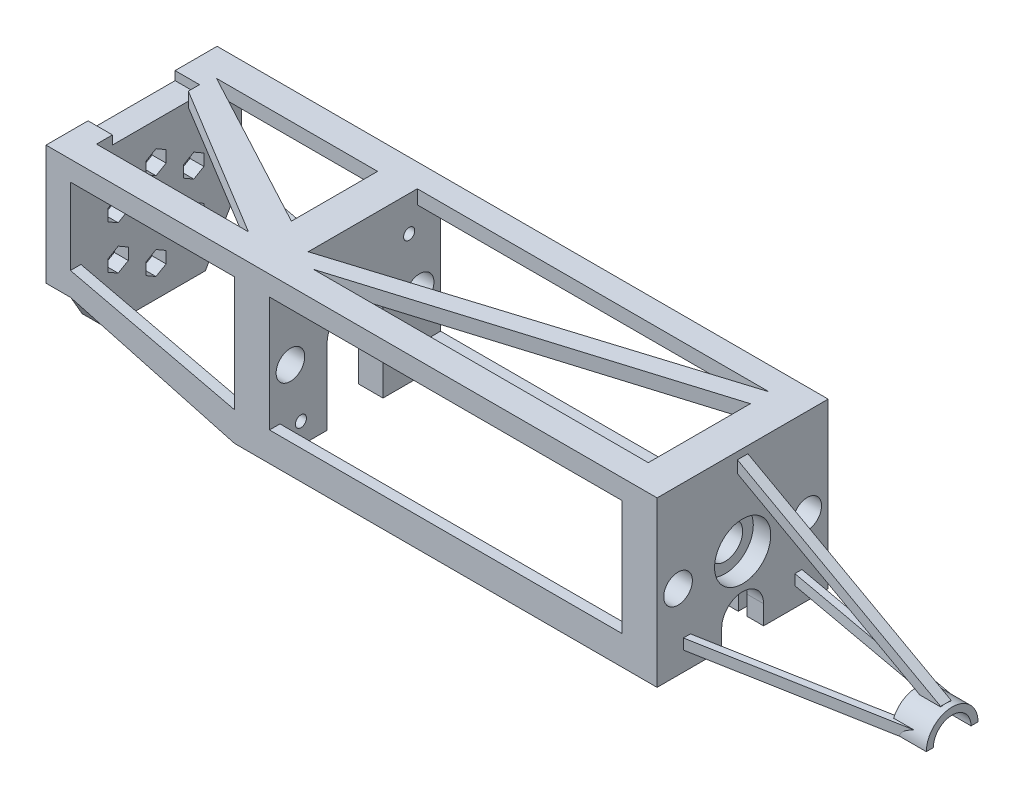
SolidWorks part; units mm, degrees
ref_plane "Front Plane" through (0, 0, 0) normal (0, 0, 1) x (1, 0, 0)
ref_plane "Top Plane" through (0, 0, 0) normal (0, 1, 0) x (1, 0, 0)
ref_plane "Right Plane" through (0, 0, 0) normal (1, 0, 0) x (0, 0, -1)
sketch "Sketch1" plane through (0, 0, 0) normal (0, 1, 0) x (1, 0, 0)
  line L0 (-33.5, 41.2067) -> (2.5, 41.2067) construction
  line L1 (-87.5, -21.5) -> (87.5, -21.5)
  line L2 (-87.5, -21.5) -> (-87.5, 21.5)
  line L3 (-87.5, 21.5) -> (87.5, 21.5)
  line L4 (87.5, -21.5) -> (87.5, 21.5)
  line L5 (-87.5, -21.5) -> (87.5, 21.5) construction
  line L6 (-87.5, 21.5) -> (87.5, -21.5) construction
  line L7 (-87.5, 21.5) -> (-80.5, 21.5)
  line L8 (-87.5, 21.5) -> (-87.5, -21.5)
  line L9 (-87.5, -21.5) -> (-80.5, -21.5)
  line L10 (-80.5, 21.5) -> (-80.5, -21.5)
  line L11 (-33.5, -21.5) -> (-23.5, -21.5)
  line L12 (-33.5, -21.5) -> (-33.5, 21.5)
  line L13 (-33.5, 21.5) -> (-23.5, 21.5)
  line L14 (-23.5, -21.5) -> (-23.5, 21.5)
  line L15 (77.5, 21.5) -> (87.5, 21.5)
  line L16 (77.5, 21.5) -> (77.5, -21.5)
  line L17 (77.5, -21.5) -> (87.5, -21.5)
  line L18 (87.5, 21.5) -> (87.5, -21.5)
  line L19 (2.5, 41.2067) -> (17.5, 41.2067) construction
  line L20 (17.5, 41.2067) -> (77.5, 41.2067) construction
  line L21 (-79.6169, 16.4596) -> (-33.5, 16.4596)
  line L22 (-33.5, 16.4596) -> (-33.5, -8.2314)
  line L23 (-33.5, -8.2314) -> (-79.6169, 16.4596)
  line L24 (-80.5, 9.2514) -> (-80.5, -17.0242)
  line L25 (-80.5, -17.0242) -> (-36.9854, -17.0242)
  line L26 (-36.9854, -17.0242) -> (-80.5, 9.2514)
  line L27 (-23.5, 17.8393) -> (-23.5, -13.4112)
  line L28 (-23.5, -13.4112) -> (77.2092, 17.8393)
  line L29 (77.2092, 17.8393) -> (-23.5, 17.8393)
  line L30 (-18.3985, -17.0242) -> (77.5, -17.0242)
  line L31 (77.5, -17.0242) -> (77.5, 12.2163)
  line L32 (77.5, 12.2163) -> (-18.3985, -17.0242)
  point P0 (0, 0)
  dimension "D1" = 43
  dimension "D2" = 7
  dimension "D3" = 10
  dimension "D4" = 10
  dimension "D5" = 47
  dimension "D6" = 121
  dimension "D7" = 36
  dimension "D8" = 15
  dimension "D9" = 60
extrude "Boss-Extrude1" add sketch "Sketch1" along normal blind 4 contours L10 L3 L2 L1 | L1 L12 L3 L10 | L1 L14 L3 L12 | L16 L3 L14 L1 | L3 L16 L1 L4 region at (-84, 0, 0) region at (-56.4148, 0, -0.0456) region at (-28.5, 0, 0) region at (27.4798, 0, 1.08) region at (82.5, 0, 0)
extrude "Boss-Extrude2" add sketch "Sketch1<3>" against normal blind 43 contours L10 L3 L2 L1 | L1 L14 L3 L12 | L3 L16 L1 L4 region at (-84, 0, 0) region at (-28.5, 0, 0) region at (82.5, 0, 0)
sketch "Sketch1<3>" plane through (0, 0, 0) normal (0, 1, 0) x (1, 0, 0) same geometry as "Sketch1"
sketch "Sketch2" plane through (-80.5, 0, 0) normal (1, 0, 0) x (0, 0, -1)
  line L1 (21.5, -43) -> (21.5, 0) construction
  line L2 (21.5, -43) -> (-21.5, -43) construction
  line L4 (-21.5, -43) -> (-21.5, 0) construction
  line L5 (21.5, -30.2609) -> (14.1451, -43)
  line L6 (21.5, -30.2609) -> (21.5, -43)
  line L7 (21.5, -43) -> (0, -43)
  line L8 (-21.5, -30.2609) -> (-21.5, -43)
  line L9 (-21.5, -43) -> (0, -43)
  line L10 (0, -34) -> (10.8253, -27.75) construction
  line L11 (10.8253, -27.75) -> (10.8253, -15.25) construction
  line L12 (10.8253, -15.25) -> (0, -9) construction
  line L13 (0, -9) -> (-10.8253, -15.25) construction
  line L14 (-10.8253, -15.25) -> (-10.8253, -27.75) construction
  line L15 (-10.8253, -27.75) -> (0, -34) construction
  line L16 (0, -21.5) -> (0, -26.3487) construction
  line L17 (-21.5, -30.2609) -> (-14.1451, -43)
  line L18 (10.8253, -27.75) -> (0, -21.5) construction
  line L19 (0, -21.5) -> (-10.8253, -27.75) construction
  line L21 (12.4609, 1.5) -> (-12.4609, 1.5)
  line L22 (12.4609, 1.5) -> (12.4609, 4)
  line L23 (12.4609, 4) -> (-12.4609, 4)
  line L24 (-12.4609, 1.5) -> (-12.4609, 4)
  line L25 (12.4609, 1.5) -> (-12.4609, 4) construction
  line L26 (12.4609, 4) -> (-12.4609, 1.5) construction
  line L27 (-21.5, 4) -> (21.5, 4) construction
  circle A2 centre (0, -21.5) radius 10.8253 construction
  circle A3 centre (-10.8253, -15.25) radius 1.55
  circle A4 centre (0, -9) radius 1.55
  circle A5 centre (10.8253, -15.25) radius 1.55
  circle A6 centre (10.8253, -27.75) radius 1.55
  circle A7 centre (0, -34) radius 1.55
  circle A8 centre (-10.8253, -27.75) radius 1.55
  point P29 (21.5, -21.5)
  point P31 (0, 0)
  point P34 (0, 2.75)
  dimension "D1" = 3.1
  dimension "D2" = 25
  dimension "D3" = 23
  dimension "D4" = 23
extrude "Cut-Extrude1" cut sketch "Sketch2" against normal blind 43 contours L14 A8 L15 | A3 | A4 | A5 | A6 | A7 | L17 A4 L6 | L5 L6 | L24 L21 L22 L23 region at (-80.5, -38.7536, -19.0484) region at (-80.5, -38.7536, 19.0484) region at (-80.5, 2.75, 0) region at (-80.5, -15.25, 10.8253) region at (-80.5, -9, 0) region at (-80.5, -15.25, -10.8253) region at (-80.5, -27.75, -10.8253) region at (-80.5, -34, 0) region at (-80.5, -27.75, 10.8253)
sketch "Sketch3" plane through (-23.5, 0, 0) normal (1, 0, 0) x (0, 0, -1)
  line L0 (-21.5, -43) -> (21.5, -43) construction
  line L1 (-15.5, -6) -> (15.5, -6) construction
  line L2 (-15.5, -6) -> (-15.5, -37) construction
  line L3 (-15.5, -37) -> (15.5, -37) construction
  line L4 (15.5, -6) -> (15.5, -37) construction
  line L5 (-15.5, -6) -> (15.5, -37) construction
  line L6 (-15.5, -37) -> (15.5, -6) construction
  line L7 (21.5, -43) -> (21.5, 0) construction
  line L8 (-18.5, -21.5) -> (18.5, -21.5) construction
  line L9 (8, -43) -> (8, -21.5)
  line L10 (-8, -43) -> (-8, -21.5)
  circle A0 centre (18.5, -21.5) radius 4.1
  circle A1 centre (-18.5, -21.5) radius 4.1
  circle A2 centre (15.5, -37) radius 1.6
  circle A3 centre (15.5, -6) radius 1.6
  circle A4 centre (-15.5, -6) radius 1.6
  circle A5 centre (-15.5, -37) radius 1.6
  circle A6 centre (0, -21.5) radius 8
  point P4 (0, -21.5)
  point P12 (0, -21.5)
  point P17 (0, -43)
  point P21 (21.5, -21.5)
  line M14 (-21.5, -43) -> (21.5, -43)
  dimension "D1" = 3.2
  dimension "D3" = 8.2
  dimension "D5" = 16
  dimension "D2" = 31
  dimension "D4" = 37
extrude "Cut-Extrude2" cut sketch "Sketch3" against normal blind 43 contours A2 | A6 | A6 L10 L9 M14 | A0 | A3 | A4 | A1 | A5 region at (-23.5, -35.2868, 0) region at (-23.5, -21.5, 0) region at (-23.5, -21.5, -18.5) region at (-23.5, -21.5, 18.5) region at (-23.5, -37, -15.5) region at (-23.5, -6, -15.5) region at (-23.5, -6, 15.5) region at (-23.5, -37, 15.5)
sketch "Sketch4" plane through (87.5, 0, 0) normal (1, 0, 0) x (0, 0, -1)
  line L0 (18.5, -21.5) -> (-18.5, -21.5) construction
  line L1 (-21.5, -43) -> (21.5, -43) construction
  line L2 (21.5, 4) -> (21.5, -43) construction
  line L3 (6, -37.5) -> (6, -43)
  line L4 (-6, -37.5) -> (-6, -43)
  line L7 (21.5, -43) -> (21.5, 0)
  circle A0 centre (18.5, -21.5) radius 4.1
  circle A1 centre (-18.5, -21.5) radius 4.1
  circle A2 centre (0, -21.5) radius 8.05
  circle A3 centre (0, -21.5) radius 5
  arc A4 (6, -37.5) -> (-6, -37.5) centre (0, -37.5) ccw
  point P4 (0, -21.5)
  point P7 (0, -43)
  point P24 (21.5, -21.5)
  point P27 (0, 0)
  line M5 (-21.5, 4) -> (-21.5, -43)
  line M6 (-21.5, -43) -> (21.5, -43)
  dimension "D1" = 8.2
  dimension "D3" = 16.1
  dimension "D4" = 10
  dimension "D5" = 6
  dimension "D2" = 37
  dimension "D6" = 16
extrude "Cut-Extrude3" cut sketch "Sketch4" against normal blind 43 contours L3 A4 L4 M6 | A3 L0 | L0 A3 | A0 | A1 region at (87.5, -37.806, 0) region at (87.5, -17.7858, -17.0381) region at (87.5, -21.5, 22.484) region at (87.5, -23.6221, 0) region at (87.5, -19.3779, 0)
extrude "Cut-Extrude4" cut sketch "Sketch4<3>" against normal blind 5 contours A2 L0 A3 | L0 A2 A3 region at (87.5, -29.37, 0) region at (87.5, -21.32, -6.525)
sketch "Sketch4<3>" plane through (87.5, 0, 0) normal (1, 0, 0) x (0, 0, -1) same geometry as "Sketch4"
sketch "Sketch6" plane through (0, 0, -21.5) normal (0, 0, -1) x (-1, 0, 0)
  line L0 (87.5, -30.2609) -> (80.5, -30.2609)
  line L1 (80.5, -30.2609) -> (33.5, -43)
  line L2 (33.5, -43) -> (23.5, -43)
  line L3 (23.5, -43) -> (-77.5, -43)
  line L4 (-77.5, -43) -> (-87.5, -43)
  line L5 (-87.5, -43) -> (-87.5, 4)
  line L6 (-87.5, 4) -> (87.5, 4)
  line L7 (87.5, 4) -> (87.5, -30.2609)
  line L32 (-77.5, -18.7054) -> (-77.5, 0) construction
  line L33 (23.5, -34.6566) -> (-77.5, -34.6566)
  line L34 (23.5, -34.6566) -> (23.5, -1.6818)
  line L35 (23.5, -1.6818) -> (-77.5, -1.6818)
  line L36 (-77.5, -34.6566) -> (-77.5, -1.6818)
  line L37 (23.5, -43) -> (23.5, -24.2946) construction
  line L38 (80.5, -30.2609) -> (80.5, 0) construction
  line L39 (80.5, -23.6015) -> (80.5, -1.6818)
  line L40 (80.5, -1.6818) -> (33.5, -1.6818)
  line L41 (33.5, -1.6818) -> (33.5, -34.6566)
  line L42 (33.5, -34.6566) -> (80.5, -23.6015)
  line L43 (33.5, -43) -> (33.5, -24.2946) construction
  line L44 (-77.5, -43) -> (-87.5, -43) construction
  line L45 (-77.5, -43) -> (-77.5, -24.2946) construction
extrude "Boss-Extrude3" add sketch "Sketch6" along normal blind 3
mirror "Mirror1" about plane through (0, 0, 0) normal (0, 0, 1) of "Boss-Extrude3"
ref_plane "Plane1" through (81.5, 0, 0) normal (1, 0, 0) x (0, 0, -1)
sketch "Sketch7" plane through (81.5, 0, 0) normal (1, 0, 0) x (0, 0, -1)
  line L0 (11.7097, -33.5) -> (1.4432, -31.1622)
  line L1 (0, -37.5) -> (0, -36.259) construction
  line L2 (12.5, -34.4905) -> (12.5, -59.658)
  line L3 (-12.5, -34.4905) -> (-12.5, -59.658)
  line L4 (-11.7097, -33.5) -> (-1.4432, -31.1622)
  line L5 (12.5, -59.658) -> (-12.5, -59.658)
  arc A0 (1.4432, -31.1622) -> (-1.4432, -31.1622) centre (0, -37.5) ccw
  arc A1 (6, -37.5) -> (-6, -37.5) centre (0, -37.5) ccw construction
  arc A2 (11.7097, -33.5) -> (12.5, -34.4905) centre (11.4841, -34.4905) cw
  arc A3 (-11.7097, -33.5) -> (-12.5, -34.4905) centre (-11.4841, -34.4905) ccw
  dimension "D1" = 6.5
  dimension "D2" = 25
  dimension "D3" = 4
extrude "Cut-Extrude6" cut sketch "Sketch7" against normal mid plane 2.5 contours L4 A3 L3 L5 L2 A2 L0 A0 region at (81.5, -45.9532, 0)
sketch "Sketch8" plane through (-33.5, 0, 0) normal (-1, 0, 0) x (0, 0, 1)
  line L0 (-11.5, -21.5) -> (-11.5, -43)
  line L1 (-8, -43) -> (-21.5, -43) construction
  line L2 (11.5, -21.5) -> (11.5, -43)
  line L3 (21.5, -43) -> (8, -43) construction
  line L4 (11.5, -43) -> (-11.5, -43)
  circle A0 centre (0, -21.5) radius 11.5
  arc A1 (8, -21.5) -> (-8, -21.5) centre (0, -21.5) ccw construction
  arc M3 (-21.5, -18.7054) -> (-21.5, -24.2946) centre (-18.5, -21.5) cw
  arc M6 (21.5, -24.2946) -> (21.5, -18.7054) centre (18.5, -21.5) cw
  line M9 (-21.5, -43) -> (-8, -43)
  line M10 (-8, -43) -> (-8, -21.5)
  arc M11 (-8, -21.5) -> (8, -21.5) centre (0, -21.5) cw
  line M12 (8, -21.5) -> (8, -43)
  line M13 (8, -43) -> (21.5, -43)
  dimension "D1" = 23
extrude "Cut-Extrude7" cut sketch "Sketch8" against normal blind 3 contours A0 M10 M12 M11 | A0 M6 M3 M10 M11 M12 | A0 L0 M3 M9 M10 | A0 L2 M12 M13 M6 | A0 M3 | A0 M6 region at (-33.5, -34.9841, -9.8691) region at (-33.5, -10.3032, 0) region at (-33.5, -34.9841, 9.8691) region at (-33.5, -23.5345, 0)
sketch "Sketch9" plane through (-80.5, 0, 0) normal (1, 0, 0) x (0, 0, -1)
  line L1 (-2.9, -32.3257) -> (-2.9, -35.6743)
  line L2 (-2.9, -35.6743) -> (0, -37.3486)
  line L3 (0, -37.3486) -> (2.9, -35.6743)
  line L4 (2.9, -35.6743) -> (2.9, -32.3257)
  line L5 (2.9, -32.3257) -> (0, -30.6514)
  line L6 (0, -30.6514) -> (-2.9, -32.3257)
  line L7 (-10.8253, -24.4014) -> (-13.7253, -26.0757)
  line L8 (-13.7253, -26.0757) -> (-13.7253, -29.4243)
  line L9 (-13.7253, -29.4243) -> (-10.8253, -31.0986)
  line L10 (-10.8253, -31.0986) -> (-7.9253, -29.4243)
  line L11 (-7.9253, -29.4243) -> (-7.9253, -26.0757)
  line L12 (-7.9253, -26.0757) -> (-10.8253, -24.4014)
  line L13 (-10.8253, -18.5986) -> (-7.9253, -16.9243)
  line L14 (-7.9253, -16.9243) -> (-7.9253, -13.5757)
  line L15 (-7.9253, -13.5757) -> (-10.8253, -11.9014)
  line L16 (-10.8253, -11.9014) -> (-13.7253, -13.5757)
  line L17 (-13.7253, -13.5757) -> (-13.7253, -16.9243)
  line L18 (-13.7253, -16.9243) -> (-10.8253, -18.5986)
  line L19 (-2.9, -7.3257) -> (-2.9, -10.6743)
  line L20 (-2.9, -10.6743) -> (0, -12.3486)
  line L21 (0, -12.3486) -> (2.9, -10.6743)
  line L22 (2.9, -10.6743) -> (2.9, -7.3257)
  line L23 (2.9, -7.3257) -> (0, -5.6514)
  line L24 (0, -5.6514) -> (-2.9, -7.3257)
  line L25 (7.9253, -13.5757) -> (7.9253, -16.9243)
  line L26 (7.9253, -16.9243) -> (10.8253, -18.5986)
  line L27 (10.8253, -18.5986) -> (13.7253, -16.9243)
  line L28 (13.7253, -16.9243) -> (13.7253, -13.5757)
  line L29 (13.7253, -13.5757) -> (10.8253, -11.9014)
  line L30 (10.8253, -11.9014) -> (7.9253, -13.5757)
  line L31 (7.9253, -26.0757) -> (7.9253, -29.4243)
  line L32 (7.9253, -29.4243) -> (10.8253, -31.0986)
  line L33 (10.8253, -31.0986) -> (13.7253, -29.4243)
  line L34 (13.7253, -29.4243) -> (13.7253, -26.0757)
  line L35 (13.7253, -26.0757) -> (10.8253, -24.4014)
  line L36 (10.8253, -24.4014) -> (7.9253, -26.0757)
  circle A0 centre (0, -34) radius 2.9 construction
  circle A1 centre (-10.8253, -27.75) radius 2.9 construction
  circle A2 centre (-10.8253, -15.25) radius 2.9 construction
  circle A3 centre (0, -9) radius 2.9 construction
  circle A4 centre (10.8253, -15.25) radius 2.9 construction
  circle A5 centre (10.8253, -27.75) radius 2.9 construction
  circle A6 centre (0, -9) radius 1.55 construction
  circle A7 centre (-10.8253, -15.25) radius 1.55 construction
  circle A8 centre (-10.8253, -27.75) radius 1.55 construction
  circle A9 centre (0, -34) radius 1.55 construction
  circle A10 centre (10.8253, -27.75) radius 1.55 construction
  circle A11 centre (10.8253, -15.25) radius 1.55 construction
  point P41 (0, -34)
  point P49 (-10.8253, -27.75)
  point P50 (-10.8253, -15.25)
  point P51 (10.8253, -27.75)
  point P52 (0, -9)
  dimension "D1" = 5.8
extrude "Cut-Extrude8" cut sketch "Sketch9" against normal blind 4
extrude "Cut-Extrude9" cut sketch "Sketch4<4>" against normal blind 150 contours L7 A0 | A1 M5 | A1 M5 | L7 A0 region at (87.5, -21.5, -18.2005) region at (87.5, -21.5, -21.9455) region at (87.5, -21.5, 18.2005) region at (87.5, -21.5, 21.9455)
sketch "Sketch4<4>" plane through (87.5, 0, 0) normal (1, 0, 0) x (0, 0, -1) same geometry as "Sketch4"
sketch "Sketch10" plane through (87.5, 0, 0) normal (1, 0, 0) x (0, 0, -1)
  line L0 (7.4, -37.5) -> (5.4, -37.5)
  line L1 (-5.4, -37.5) -> (-7.4, -37.5)
  arc A0 (5.4, -37.5) -> (-5.4, -37.5) centre (0, -37.5) ccw
  arc A1 (7.4, -37.5) -> (-7.4, -37.5) centre (0, -37.5) ccw
  arc A3 (6, -37.5) -> (-6, -37.5) centre (0, -37.5) ccw construction
  point P3 (0, 0)
  point P9 (0, -38.5856)
  point P10 (6.4989, -34.9116)
  point P11 (-6, -37.5)
  point P13 (0, 0)
  point P14 (0, 0)
  point P15 (-5.3251, -37.5643)
  dimension "D2" = 5.4
  dimension "D1" = 2
extrude "Boss-Extrude4" add sketch "Sketch10" along normal blind 60
extrude "Cut-Extrude10" cut sketch "Sketch10<2>" along normal blind 50
sketch "Sketch10<2>" plane through (87.5, 0, 0) normal (1, 0, 0) x (0, 0, -1) same geometry as "Sketch10"
sketch "Sketch12" plane through (0, 0, 0) normal (0, 0, 1) x (1, 0, 0)
  line L0 (139.486, -30.1) -> (87.5, -1.477)
  line L1 (87.5, -1.477) -> (87.5, 1.9476)
  line L2 (87.5, 1.9476) -> (145.706, -30.1)
  line L3 (145.706, -30.1) -> (139.486, -30.1)
  line L6 (87.5, 4) -> (87.5, -43) construction
  line L7 (139.486, -30.1) -> (139.486, -31.1)
  line L8 (139.486, -31.1) -> (145.8085, -31.1)
  line L9 (145.8085, -31.1) -> (145.706, -30.1)
  point P3 (137.5, -30.1)
  point P5 (145.8085, -30.2017)
  point P6 (147.5, -30.1)
  point P13 (139.486, -30.3443)
  dimension "D1" = 3
  dimension "D2" = 1
extrude "Boss-Extrude5" add sketch "Sketch12" along normal mid plane 3 contours L3 L2 L1 L0 | L8 L9 L3 L7 region at (115.0773, -14.9162, 0) region at (142.6217, -30.6014, 0)
sketch "Sketch13" plane through (0, -37.5, 0) normal (0, -1, 0) x (1, 0, 0)
  line L0 (87.5, -16.9812) -> (87.5, -14.948)
  line L1 (87.5, -14.948) -> (139.6691, -5.4)
  line L2 (147.5, -5.4) -> (137.5, -5.4) construction
  line L3 (139.6691, -5.4) -> (147.5, -6)
  line L4 (147.5, -6) -> (87.5, -16.9812)
  line L5 (87.5, -6) -> (87.5, -24.5) construction
  point P8 (87.5, -19.7255)
  point P9 (147.5, -6)
  dimension "D1" = 2
extrude "Boss-Extrude6" add sketch "Sketch13" against normal blind 3
mirror "Mirror2" about plane through (0, 0, 0) normal (0, 0, 1) of "Boss-Extrude6"
